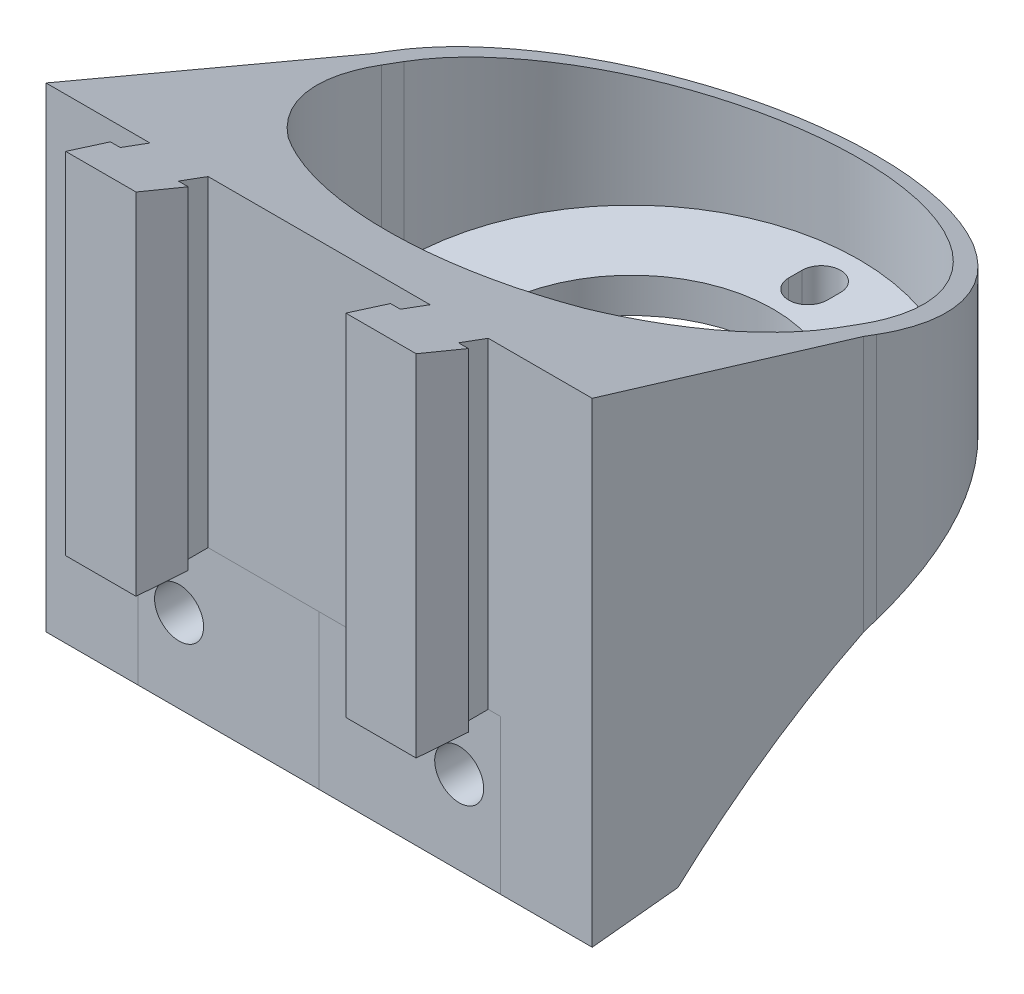
SolidWorks part; units mm, degrees
ref_plane "Front Plane" through (0, 0, 0) normal (0, 0, 1) x (1, 0, 0)
ref_plane "Top Plane" through (0, 0, 0) normal (0, 1, 0) x (1, 0, 0)
ref_plane "Right Plane" through (0, 0, 0) normal (1, 0, 0) x (0, 0, -1)
sketch "Sketch1" plane through (0, 0, 0) normal (0, 1, 0) x (1, 0, 0)
  line L208 (0, 28.6911) -> (0, 71.6911) construction
  line L209 (0, 59.2911) -> (-47.2537, 59.2911) construction
  line L210 (16.6412, 0.931) -> (17.2272, 1.5169) construction
  line L211 (14.3988, 4.3454) -> (13.8128, 3.7594) construction
  line L212 (13.8128, 10.4769) -> (14.3988, 9.891) construction
  line L213 (17.2272, 12.7194) -> (16.6412, 13.3054) construction
  line L214 (23.3588, 13.3054) -> (22.7728, 12.7194) construction
  line L215 (25.6012, 9.891) -> (26.1872, 10.4769) construction
  line L216 (26.1872, 3.7594) -> (25.6012, 4.3454) construction
  line L217 (22.7728, 1.5169) -> (23.3588, 0.931) construction
  line L218 (-29.6, -20.9818) -> (-29.6, -4.7818) construction
  line L219 (-38, -20.9818) -> (-29.6, -20.9818) construction
  line L220 (-38, -4.7818) -> (-38, -20.9818) construction
  line L221 (-29.6, -4.7818) -> (-38, -4.7818) construction
  line L222 (-23.3588, 0.931) -> (-22.7728, 1.5169) construction
  line L223 (-25.6012, 4.3454) -> (-26.1872, 3.7594) construction
  line L224 (-26.1872, 10.4769) -> (-25.6012, 9.891) construction
  line L225 (-22.7728, 12.7194) -> (-23.3588, 13.3054) construction
  line L226 (-16.6412, 13.3054) -> (-17.2272, 12.7194) construction
  line L227 (-14.3988, 9.891) -> (-13.8128, 10.4769) construction
  line L228 (-13.8128, 3.7594) -> (-14.3988, 4.3454) construction
  line L229 (-17.2272, 1.5169) -> (-16.6412, 0.931) construction
  line L230 (23.3588, -26.6946) -> (22.7728, -27.2806) construction
  line L231 (25.6012, -30.109) -> (26.1872, -29.5231) construction
  line L232 (26.1872, -36.2406) -> (25.6012, -35.6546) construction
  line L233 (22.7728, -38.4831) -> (23.3588, -39.069) construction
  line L234 (16.6412, -39.069) -> (17.2272, -38.4831) construction
  line L235 (14.3988, -35.6546) -> (13.8128, -36.2406) construction
  line L236 (13.8128, -29.5231) -> (14.3988, -30.109) construction
  line L237 (17.2272, -27.2806) -> (16.6412, -26.6946) construction
  line L238 (-31.2, -44.0818) -> (-38.4, -44.0818) construction
  line L239 (-31.2, -51.2818) -> (-31.2, -44.0818) construction
  line L240 (-38.4, -51.2818) -> (-31.2, -51.2818) construction
  line L241 (-38.4, -44.0818) -> (-38.4, -51.2818) construction
  line L242 (-16.6412, -26.6946) -> (-17.2272, -27.2806) construction
  line L243 (-14.3988, -30.109) -> (-13.8128, -29.5231) construction
  line L244 (-13.8128, -36.2406) -> (-14.3988, -35.6546) construction
  line L245 (-17.2272, -38.4831) -> (-16.6412, -39.069) construction
  line L246 (-23.3588, -39.069) -> (-22.7728, -38.4831) construction
  line L247 (-25.6012, -35.6546) -> (-26.1872, -36.2406) construction
  line L248 (-26.1872, -29.5231) -> (-25.6012, -30.109) construction
  line L249 (-22.7728, -27.2806) -> (-23.3588, -26.6946) construction
  line L250 (-38.4, 18.3182) -> (-31.2, 18.3182) construction
  line L251 (-38.4, 25.5182) -> (-38.4, 18.3182) construction
  line L252 (-31.2, 25.5182) -> (-38.4, 25.5182) construction
  line L253 (-31.2, 18.3182) -> (-31.2, 25.5182) construction
  line L254 (38.4, -44.0818) -> (31.2, -44.0818) construction
  line L255 (38.4, -51.2818) -> (38.4, -44.0818) construction
  line L256 (31.2, -51.2818) -> (38.4, -51.2818) construction
  line L257 (31.2, -44.0818) -> (31.2, -51.2818) construction
  line L258 (31.2, 18.2278) -> (38.4, 18.2278) construction
  line L259 (31.2, 25.5182) -> (31.2, 18.2278) construction
  line L260 (38.4, 25.5182) -> (31.2, 25.5182) construction
  line L261 (38.4, 18.2278) -> (38.4, 25.5182) construction
  line L262 (-8.1, 25.1182) -> (-8.1, 16.7182) construction
  line L263 (8.1, 25.1182) -> (-8.1, 25.1182) construction
  line L264 (8.1, 16.7182) -> (8.1, 25.1182) construction
  line L265 (-8.1, 16.7182) -> (8.1, 16.7182) construction
  line L266 (11.2, -37.6818) -> (11.2, -28.0818) construction
  line L267 (-9.2, -39.6818) -> (9.2, -39.6818) construction
  line L268 (-11.2, -28.0818) -> (-11.2, -37.6818) construction
  line L269 (-24.8, -24.0818) -> (-15.2, -24.0818) construction
  line L270 (-26.8, -3.6818) -> (-26.8, -22.0818) construction
  line L271 (-15.2, -1.6818) -> (-24.8, -1.6818) construction
  line L272 (-11.2, 11.9182) -> (-11.2, 2.3182) construction
  line L273 (9.2, 13.9182) -> (-9.2, 13.9182) construction
  line L274 (11.2, 2.3182) -> (11.2, 11.9182) construction
  line L275 (24.8, -1.6818) -> (15.2, -1.6818) construction
  line L276 (26.8, -22.0818) -> (26.8, -3.6818) construction
  line L277 (15.2, -24.0818) -> (24.8, -24.0818) construction
  line L278 (8.1, -42.4818) -> (-8.1, -42.4818) construction
  line L279 (8.1, -50.8818) -> (8.1, -42.4818) construction
  line L280 (-8.1, -50.8818) -> (8.1, -50.8818) construction
  line L281 (-8.1, -42.4818) -> (-8.1, -50.8818) construction
  line L282 (29.6, -4.7818) -> (29.6, -20.9818) construction
  line L283 (38, -4.7818) -> (29.6, -4.7818) construction
  line L284 (38, -20.9818) -> (38, -4.7818) construction
  line L285 (29.6, -20.9818) -> (38, -20.9818) construction
  line L286 (40, -51.8818) -> (40, -38.1318) construction
  line L287 (40, -38.1318) -> (39, -37.1318) construction
  line L288 (39, -37.1318) -> (36, -37.1318) construction
  line L289 (36, -37.1318) -> (36, -40.1318) construction
  line L290 (36, -40.1318) -> (37.6041, -40.1318) construction
  line L291 (38.0965, -40.7186) -> (37.9168, -41.7381) construction
  line L292 (37.0304, -42.4818) -> (32.3339, -42.4818) construction
  line L293 (30.2125, -41.6031) -> (29.6787, -41.0693) construction
  line L294 (28.8, -38.9479) -> (28.8, -26.8157) construction
  line L295 (29.6787, -24.6944) -> (30.2125, -24.1605) construction
  line L296 (32.3339, -23.2818) -> (37.0304, -23.2818) construction
  line L297 (37.9168, -24.0255) -> (38.0965, -25.045) construction
  line L298 (37.6041, -25.6318) -> (36, -25.6318) construction
  line L299 (36, -25.6318) -> (36, -28.6318) construction
  line L300 (36, -28.6318) -> (39, -28.6318) construction
  line L301 (39, -28.6318) -> (40, -27.6318) construction
  line L302 (40, -27.6318) -> (40, 1.8682) construction
  line L303 (40, 1.8682) -> (39, 2.8682) construction
  line L304 (39, 2.8682) -> (36, 2.8682) construction
  line L305 (36, 2.8682) -> (36, -0.1318) construction
  line L306 (36, -0.1318) -> (37.6041, -0.1318) construction
  line L307 (38.0965, -0.7186) -> (37.9168, -1.7381) construction
  line L308 (37.0304, -2.4818) -> (32.3339, -2.4818) construction
  line L309 (30.2125, -1.6031) -> (29.6787, -1.0693) construction
  line L310 (28.8, 1.0521) -> (28.8, 13.1843) construction
  line L311 (29.6787, 15.3056) -> (30.2125, 15.8395) construction
  line L312 (32.3339, 16.7182) -> (37.0304, 16.7182) construction
  line L313 (37.9168, 15.9745) -> (38.0965, 14.955) construction
  line L314 (37.6041, 14.3682) -> (36, 14.3682) construction
  line L315 (36, 14.3682) -> (36, 9.7607) construction
  line L316 (36, 9.7607) -> (39, 9.7607) construction
  line L317 (39, 9.7607) -> (40, 10.7607) construction
  line L318 (40, 10.7607) -> (40, 26.0836) construction
  line L319 (39, 27.0836) -> (25.25, 27.0836) construction
  line L320 (25.25, 27.0836) -> (24.25, 26.0836) construction
  line L321 (24.25, 26.0836) -> (24.25, 23.0836) construction
  line L322 (24.25, 23.0836) -> (27.25, 23.0836) construction
  line L323 (27.25, 23.0836) -> (27.25, 26.2607) construction
  line L324 (27.8368, 26.7531) -> (28.8563, 26.5733) construction
  line L325 (29.6, 25.687) -> (29.6, 19.4175) construction
  line L326 (28.7213, 17.2962) -> (28.1875, 16.7623) construction
  line L327 (26.0661, 15.8836) -> (13.9339, 15.8836) construction
  line L328 (11.8125, 16.7623) -> (11.2787, 17.2962) construction
  line L329 (10.4, 19.4175) -> (10.4, 24.1141) construction
  line L330 (11.1437, 25.0004) -> (12.1632, 25.1801) construction
  line L331 (12.75, 24.6877) -> (12.75, 23.0836) construction
  line L332 (12.75, 23.0836) -> (17.1652, 23.0836) construction
  line L333 (17.1652, 23.0836) -> (17.1652, 26.2414) construction
  line L334 (17.1652, 26.2414) -> (16.3229, 27.0836) construction
  line L335 (16.3229, 27.0836) -> (-14.75, 27.0836) construction
  line L336 (-14.75, 27.0836) -> (-15.75, 26.0836) construction
  line L337 (-15.75, 26.0836) -> (-15.75, 23.0836) construction
  line L338 (-15.75, 23.0836) -> (-12.75, 23.0836) construction
  line L339 (-12.75, 23.0836) -> (-12.75, 24.7223) construction
  line L340 (-12.1632, 25.2147) -> (-11.1437, 25.035) construction
  line L341 (-10.4, 24.1486) -> (-10.4, 19.4521) construction
  line L342 (-11.2787, 17.3307) -> (-11.8125, 16.7969) construction
  line L343 (-13.9339, 15.9182) -> (-26.0661, 15.9182) construction
  line L344 (-28.1875, 16.7969) -> (-28.7213, 17.3307) construction
  line L345 (-29.6, 19.4521) -> (-29.6, 24.1486) construction
  line L346 (-28.8563, 25.035) -> (-27.8368, 25.2147) construction
  line L347 (-27.25, 24.7223) -> (-27.25, 23.1182) construction
  line L348 (-27.25, 23.1182) -> (-24.25, 23.1182) construction
  line L349 (-24.25, 23.1182) -> (-24.25, 26.1182) construction
  line L350 (-24.25, 26.1182) -> (-25.25, 27.1182) construction
  line L351 (-25.25, 27.1182) -> (-39, 27.1182) construction
  line L352 (-40, 26.1182) -> (-40, 12.3682) construction
  line L353 (-40, 12.3682) -> (-39, 11.3682) construction
  line L354 (-39, 11.3682) -> (-36, 11.3682) construction
  line L355 (-36, 11.3682) -> (-36, 14.3682) construction
  line L356 (-36, 14.3682) -> (-37.6041, 14.3682) construction
  line L357 (-38.0965, 14.955) -> (-37.9168, 15.9745) construction
  line L358 (-37.0304, 16.7182) -> (-32.3339, 16.7182) construction
  line L359 (-30.2125, 15.8395) -> (-29.6787, 15.3056) construction
  line L360 (-28.8, 13.1843) -> (-28.8, 1.0521) construction
  line L361 (-29.6787, -1.0693) -> (-30.2125, -1.6031) construction
  line L362 (-32.3339, -2.4818) -> (-37.0304, -2.4818) construction
  line L363 (-37.9168, -1.7381) -> (-38.0965, -0.7186) construction
  line L364 (-37.6041, -0.1318) -> (-36, -0.1318) construction
  line L365 (-36, -0.1318) -> (-36, 2.8682) construction
  line L366 (-36, 2.8682) -> (-39, 2.8682) construction
  line L367 (-39, 2.8682) -> (-40, 1.8682) construction
  line L368 (-40, 1.8682) -> (-40, -27.6318) construction
  line L369 (-40, -27.6318) -> (-39, -28.6318) construction
  line L370 (-39, -28.6318) -> (-36, -28.6318) construction
  line L371 (-36, -28.6318) -> (-36, -25.6318) construction
  line L372 (-36, -25.6318) -> (-37.6041, -25.6318) construction
  line L373 (-38.0965, -25.045) -> (-37.9168, -24.0255) construction
  line L374 (-37.0304, -23.2818) -> (-32.3339, -23.2818) construction
  line L375 (-30.2125, -24.1605) -> (-29.6787, -24.6944) construction
  line L376 (-28.8, -26.8157) -> (-28.8, -38.9479) construction
  line L377 (-29.6787, -41.0693) -> (-30.2125, -41.6031) construction
  line L378 (-32.3339, -42.4818) -> (-37.0304, -42.4818) construction
  line L379 (-37.9168, -41.7381) -> (-38.0965, -40.7186) construction
  line L380 (-37.6041, -40.1318) -> (-36, -40.1318) construction
  line L381 (-36, -40.1318) -> (-36, -37.1318) construction
  line L382 (-36, -37.1318) -> (-39, -37.1318) construction
  line L383 (-39, -37.1318) -> (-40, -38.1318) construction
  line L384 (-40, -38.1318) -> (-40, -51.8818) construction
  line L385 (-39, -52.8818) -> (-25.25, -52.8818) construction
  line L386 (-25.25, -52.8818) -> (-24.25, -51.8818) construction
  line L387 (-24.25, -51.8818) -> (-24.25, -48.8818) construction
  line L388 (-24.25, -48.8818) -> (-27.25, -48.8818) construction
  line L389 (-27.25, -48.8818) -> (-27.25, -50.4859) construction
  line L390 (-27.8368, -50.9783) -> (-28.8563, -50.7986) construction
  line L391 (-29.6, -49.9123) -> (-29.6, -45.2157) construction
  line L392 (-28.7213, -43.0944) -> (-28.1875, -42.5605) construction
  line L393 (-26.0661, -41.6818) -> (-13.9339, -41.6818) construction
  line L394 (-11.8125, -42.5605) -> (-11.2787, -43.0944) construction
  line L395 (-10.4, -45.2157) -> (-10.4, -49.9123) construction
  line L396 (-11.1437, -50.7986) -> (-12.1632, -50.9783) construction
  line L397 (-12.75, -50.4859) -> (-12.75, -48.8818) construction
  line L398 (-12.75, -48.8818) -> (-15.75, -48.8818) construction
  line L399 (-15.75, -48.8818) -> (-15.75, -51.8818) construction
  line L400 (-15.75, -51.8818) -> (-14.75, -52.8818) construction
  line L401 (-14.75, -52.8818) -> (14.75, -52.8818) construction
  line L402 (14.75, -52.8818) -> (15.75, -51.8818) construction
  line L403 (15.75, -51.8818) -> (15.75, -48.8818) construction
  line L404 (15.75, -48.8818) -> (12.75, -48.8818) construction
  line L405 (12.75, -48.8818) -> (12.75, -50.4859) construction
  line L406 (12.1632, -50.9783) -> (11.1437, -50.7986) construction
  line L407 (10.4, -49.9123) -> (10.4, -45.2157) construction
  line L408 (11.2787, -43.0944) -> (11.8125, -42.5605) construction
  line L409 (13.9339, -41.6818) -> (26.0661, -41.6818) construction
  line L410 (28.1875, -42.5605) -> (28.7213, -43.0944) construction
  line L411 (29.6, -45.2157) -> (29.6, -49.9123) construction
  line L412 (28.8563, -50.7986) -> (27.8368, -50.9783) construction
  line L413 (27.25, -50.4859) -> (27.25, -48.8818) construction
  line L414 (27.25, -48.8818) -> (24.25, -48.8818) construction
  line L415 (24.25, -48.8818) -> (24.25, -51.8818) construction
  line L416 (24.25, -51.8818) -> (25.25, -52.8818) construction
  line L417 (25.25, -52.8818) -> (39, -52.8818) construction
  line L418 (0, 71.6911) -> (0, 68.4761) construction
  line L419 (34.9935, 71.6911) -> (34.9935, 68.4761)
  line L420 (-34.9935, 71.6911) -> (-34.9935, 68.4761)
  line L421 (0, 71.6911) -> (0, 70.0836) construction
  line L422 (32.9959, 71.6911) -> (32.9959, 70.0836) construction
  line L423 (-32.9959, 71.6911) -> (-32.9959, 70.0836) construction
  line L424 (-34.9935, 70.0836) -> (-34.8, 27.1182) construction
  line L427 (27.1, 71.6911) -> (27.0834, 67.963) construction
  line L430 (0, 71.6911) -> (0, 68.4761) construction
  line L431 (32.5, 71.6911) -> (32.5, 68.4761)
  line L432 (-32.5, 71.6911) -> (-32.5, 68.4761)
  line L433 (0, 71.6911) -> (0, 68.4761) construction
  line L436 (0, 98.7911) -> (0, 96.8911) construction
  line L437 (2.75, 98.7911) -> (2.75, 96.8911)
  line L438 (-2.75, 98.7911) -> (-2.75, 96.8911)
  line L439 (0, 70.0836) -> (54.1857, 70.0836) construction
  line L440 (0, 41.3761) -> (0, 43.2761) construction
  line L443 (0, 71.6911) -> (0, 68.4761) construction
  line L444 (20.25, 71.6911) -> (20.25, 68.4761)
  line L445 (-20.25, 71.6911) -> (-20.25, 68.4761)
  line L446 (2.75, 41.3761) -> (2.75, 43.2761)
  line L447 (-2.75, 41.3761) -> (-2.75, 43.2761)
  line L448 (25.6055, 71.0336) -> (25.597, 69.1336) construction
  line L449 (28.3555, 71.0214) -> (28.347, 69.1214)
  line L450 (22.8555, 71.0459) -> (22.847, 69.1459)
  line L451 (-25.6055, 71.0336) -> (-25.597, 69.1336) construction
  line L452 (-28.3555, 71.0214) -> (-28.347, 69.1214)
  line L453 (-22.8555, 71.0459) -> (-22.847, 69.1459)
  circle A112 centre (0, 71.6911) radius 12.4 construction
  arc A113 (0, 38.6911) -> (-30.5817, 59.2911) centre (0, 71.6911) ccw construction
  circle A114 centre (0, 71.6911) radius 20.25 construction
  arc A115 (34.9935, 71.0158) -> (-34.9935, 71.0158) centre (0, 71.6911) ccw construction
  circle A116 centre (0, 71.6911) radius 27.1 construction
  circle A117 centre (0, 98.7911) radius 1.9 construction
  circle A118 centre (-27.1, 71.6911) radius 1.9 construction
  circle A119 centre (0, 44.5911) radius 1.9 construction
  circle A120 centre (27.1, 71.6911) radius 1.9 construction
  arc A121 (17.2272, 1.5169) -> (22.7728, 1.5169) centre (20, 7.1182) ccw construction
  arc A122 (13.8128, 3.7594) -> (16.6412, 0.931) centre (15.227, 2.3452) ccw construction
  arc A123 (14.3988, 9.891) -> (14.3988, 4.3454) centre (20, 7.1182) ccw construction
  arc A124 (16.6412, 13.3054) -> (13.8128, 10.4769) centre (15.227, 11.8912) ccw construction
  arc A125 (22.7728, 12.7194) -> (17.2272, 12.7194) centre (20, 7.1182) ccw construction
  arc A126 (26.1872, 10.4769) -> (23.3588, 13.3054) centre (24.773, 11.8912) ccw construction
  arc A127 (25.6012, 4.3454) -> (25.6012, 9.891) centre (20, 7.1182) ccw construction
  arc A128 (23.3588, 0.931) -> (26.1872, 3.7594) centre (24.773, 2.3452) ccw construction
  arc A129 (-22.7728, 1.5169) -> (-17.2272, 1.5169) centre (-20, 7.1182) ccw construction
  arc A130 (-26.1872, 3.7594) -> (-23.3588, 0.931) centre (-24.773, 2.3452) ccw construction
  arc A131 (-25.6012, 9.891) -> (-25.6012, 4.3454) centre (-20, 7.1182) ccw construction
  arc A132 (-23.3588, 13.3054) -> (-26.1872, 10.4769) centre (-24.773, 11.8912) ccw construction
  arc A133 (-17.2272, 12.7194) -> (-22.7728, 12.7194) centre (-20, 7.1182) ccw construction
  arc A134 (-13.8128, 10.4769) -> (-16.6412, 13.3054) centre (-15.227, 11.8912) ccw construction
  arc A135 (-14.3988, 4.3454) -> (-14.3988, 9.891) centre (-20, 7.1182) ccw construction
  arc A136 (-16.6412, 0.931) -> (-13.8128, 3.7594) centre (-15.227, 2.3452) ccw construction
  arc A137 (22.7728, -27.2806) -> (17.2272, -27.2806) centre (20, -32.8818) ccw construction
  arc A138 (26.1872, -29.5231) -> (23.3588, -26.6946) centre (24.773, -28.1088) ccw construction
  arc A139 (25.6012, -35.6546) -> (25.6012, -30.109) centre (20, -32.8818) ccw construction
  arc A140 (23.3588, -39.069) -> (26.1872, -36.2406) centre (24.773, -37.6548) ccw construction
  arc A141 (17.2272, -38.4831) -> (22.7728, -38.4831) centre (20, -32.8818) ccw construction
  arc A142 (13.8128, -36.2406) -> (16.6412, -39.069) centre (15.227, -37.6548) ccw construction
  arc A143 (14.3988, -30.109) -> (14.3988, -35.6546) centre (20, -32.8818) ccw construction
  arc A144 (16.6412, -26.6946) -> (13.8128, -29.5231) centre (15.227, -28.1088) ccw construction
  arc A145 (-17.2272, -27.2806) -> (-22.7728, -27.2806) centre (-20, -32.8818) ccw construction
  arc A146 (-13.8128, -29.5231) -> (-16.6412, -26.6946) centre (-15.227, -28.1088) ccw construction
  arc A147 (-14.3988, -35.6546) -> (-14.3988, -30.109) centre (-20, -32.8818) ccw construction
  arc A148 (-16.6412, -39.069) -> (-13.8128, -36.2406) centre (-15.227, -37.6548) ccw construction
  arc A149 (-22.7728, -38.4831) -> (-17.2272, -38.4831) centre (-20, -32.8818) ccw construction
  arc A150 (-26.1872, -36.2406) -> (-23.3588, -39.069) centre (-24.773, -37.6548) ccw construction
  arc A151 (-25.6012, -30.109) -> (-25.6012, -35.6546) centre (-20, -32.8818) ccw construction
  arc A152 (-23.3588, -26.6946) -> (-26.1872, -29.5231) centre (-24.773, -28.1088) ccw construction
  arc A153 (15.2, -24.0818) -> (11.2, -28.0818) centre (15.2, -28.0818) ccw construction
  arc A154 (9.2, -39.6818) -> (11.2, -37.6818) centre (9.2, -37.6818) ccw construction
  arc A155 (-11.2, -37.6818) -> (-9.2, -39.6818) centre (-9.2, -37.6818) ccw construction
  arc A156 (-11.2, -28.0818) -> (-15.2, -24.0818) centre (-15.2, -28.0818) ccw construction
  arc A157 (-26.8, -22.0818) -> (-24.8, -24.0818) centre (-24.8, -22.0818) ccw construction
  arc A158 (-24.8, -1.6818) -> (-26.8, -3.6818) centre (-24.8, -3.6818) ccw construction
  arc A159 (-15.2, -1.6818) -> (-11.2, 2.3182) centre (-15.2, 2.3182) ccw construction
  arc A160 (-9.2, 13.9182) -> (-11.2, 11.9182) centre (-9.2, 11.9182) ccw construction
  arc A161 (11.2, 11.9182) -> (9.2, 13.9182) centre (9.2, 11.9182) ccw construction
  arc A162 (11.2, 2.3182) -> (15.2, -1.6818) centre (15.2, 2.3182) ccw construction
  arc A163 (26.8, -3.6818) -> (24.8, -1.6818) centre (24.8, -3.6818) ccw construction
  arc A164 (24.8, -24.0818) -> (26.8, -22.0818) centre (24.8, -22.0818) ccw construction
  arc A165 (39, -52.8818) -> (40, -51.8818) centre (39, -51.8818) ccw construction
  arc A166 (38.0965, -40.7186) -> (37.6041, -40.1318) centre (37.6041, -40.6318) ccw construction
  arc A167 (37.0304, -42.4818) -> (37.9168, -41.7381) centre (37.0304, -41.5818) ccw construction
  arc A168 (30.2125, -41.6031) -> (32.3339, -42.4818) centre (32.3339, -39.4818) ccw construction
  arc A169 (28.8, -38.9479) -> (29.6787, -41.0693) centre (31.8, -38.9479) ccw construction
  arc A170 (29.6787, -24.6944) -> (28.8, -26.8157) centre (31.8, -26.8157) ccw construction
  arc A171 (32.3339, -23.2818) -> (30.2125, -24.1605) centre (32.3339, -26.2818) ccw construction
  arc A172 (37.9168, -24.0255) -> (37.0304, -23.2818) centre (37.0304, -24.1818) ccw construction
  arc A173 (37.6041, -25.6318) -> (38.0965, -25.045) centre (37.6041, -25.1318) ccw construction
  arc A174 (38.0965, -0.7186) -> (37.6041, -0.1318) centre (37.6041, -0.6318) ccw construction
  arc A175 (37.0304, -2.4818) -> (37.9168, -1.7381) centre (37.0304, -1.5818) ccw construction
  arc A176 (30.2125, -1.6031) -> (32.3339, -2.4818) centre (32.3339, 0.5182) ccw construction
  arc A177 (28.8, 1.0521) -> (29.6787, -1.0693) centre (31.8, 1.0521) ccw construction
  arc A178 (29.6787, 15.3056) -> (28.8, 13.1843) centre (31.8, 13.1843) ccw construction
  arc A179 (32.3339, 16.7182) -> (30.2125, 15.8395) centre (32.3339, 13.7182) ccw construction
  arc A180 (37.9168, 15.9745) -> (37.0304, 16.7182) centre (37.0304, 15.8182) ccw construction
  arc A181 (37.6041, 14.3682) -> (38.0965, 14.955) centre (37.6041, 14.8682) ccw construction
  arc A182 (40, 26.0836) -> (39, 27.0836) centre (39, 26.0836) ccw construction
  arc A183 (27.8368, 26.7531) -> (27.25, 26.2607) centre (27.75, 26.2607) ccw construction
  arc A184 (29.6, 25.687) -> (28.8563, 26.5733) centre (28.7, 25.687) ccw construction
  arc A185 (28.7213, 17.2962) -> (29.6, 19.4175) centre (26.6, 19.4175) ccw construction
  arc A186 (26.0661, 15.8836) -> (28.1875, 16.7623) centre (26.0661, 18.8836) ccw construction
  arc A187 (11.8125, 16.7623) -> (13.9339, 15.8836) centre (13.9339, 18.8836) ccw construction
  arc A188 (10.4, 19.4175) -> (11.2787, 17.2962) centre (13.4, 19.4175) ccw construction
  arc A189 (11.1437, 25.0004) -> (10.4, 24.1141) centre (11.3, 24.1141) ccw construction
  arc A190 (12.75, 24.6877) -> (12.1632, 25.1801) centre (12.25, 24.6877) ccw construction
  arc A191 (-12.1632, 25.2147) -> (-12.75, 24.7223) centre (-12.25, 24.7223) ccw construction
  arc A192 (-10.4, 24.1486) -> (-11.1437, 25.035) centre (-11.3, 24.1486) ccw construction
  arc A193 (-11.2787, 17.3307) -> (-10.4, 19.4521) centre (-13.4, 19.4521) ccw construction
  arc A194 (-13.9339, 15.9182) -> (-11.8125, 16.7969) centre (-13.9339, 18.9182) ccw construction
  arc A195 (-28.1875, 16.7969) -> (-26.0661, 15.9182) centre (-26.0661, 18.9182) ccw construction
  arc A196 (-29.6, 19.4521) -> (-28.7213, 17.3307) centre (-26.6, 19.4521) ccw construction
  arc A197 (-28.8563, 25.035) -> (-29.6, 24.1486) centre (-28.7, 24.1486) ccw construction
  arc A198 (-27.25, 24.7223) -> (-27.8368, 25.2147) centre (-27.75, 24.7223) ccw construction
  arc A199 (-39, 27.1182) -> (-40, 26.1182) centre (-39, 26.1182) ccw construction
  arc A200 (-38.0965, 14.955) -> (-37.6041, 14.3682) centre (-37.6041, 14.8682) ccw construction
  arc A201 (-37.0304, 16.7182) -> (-37.9168, 15.9745) centre (-37.0304, 15.8182) ccw construction
  arc A202 (-30.2125, 15.8395) -> (-32.3339, 16.7182) centre (-32.3339, 13.7182) ccw construction
  arc A203 (-28.8, 13.1843) -> (-29.6787, 15.3056) centre (-31.8, 13.1843) ccw construction
  arc A204 (-29.6787, -1.0693) -> (-28.8, 1.0521) centre (-31.8, 1.0521) ccw construction
  arc A205 (-32.3339, -2.4818) -> (-30.2125, -1.6031) centre (-32.3339, 0.5182) ccw construction
  arc A206 (-37.9168, -1.7381) -> (-37.0304, -2.4818) centre (-37.0304, -1.5818) ccw construction
  arc A207 (-37.6041, -0.1318) -> (-38.0965, -0.7186) centre (-37.6041, -0.6318) ccw construction
  arc A208 (-38.0965, -25.045) -> (-37.6041, -25.6318) centre (-37.6041, -25.1318) ccw construction
  arc A209 (-37.0304, -23.2818) -> (-37.9168, -24.0255) centre (-37.0304, -24.1818) ccw construction
  arc A210 (-30.2125, -24.1605) -> (-32.3339, -23.2818) centre (-32.3339, -26.2818) ccw construction
  arc A211 (-28.8, -26.8157) -> (-29.6787, -24.6944) centre (-31.8, -26.8157) ccw construction
  arc A212 (-29.6787, -41.0693) -> (-28.8, -38.9479) centre (-31.8, -38.9479) ccw construction
  arc A213 (-32.3339, -42.4818) -> (-30.2125, -41.6031) centre (-32.3339, -39.4818) ccw construction
  arc A214 (-37.9168, -41.7381) -> (-37.0304, -42.4818) centre (-37.0304, -41.5818) ccw construction
  arc A215 (-37.6041, -40.1318) -> (-38.0965, -40.7186) centre (-37.6041, -40.6318) ccw construction
  arc A216 (-40, -51.8818) -> (-39, -52.8818) centre (-39, -51.8818) ccw construction
  arc A217 (-27.8368, -50.9783) -> (-27.25, -50.4859) centre (-27.75, -50.4859) ccw construction
  arc A218 (-29.6, -49.9123) -> (-28.8563, -50.7986) centre (-28.7, -49.9123) ccw construction
  arc A219 (-28.7213, -43.0944) -> (-29.6, -45.2157) centre (-26.6, -45.2157) ccw construction
  arc A220 (-26.0661, -41.6818) -> (-28.1875, -42.5605) centre (-26.0661, -44.6818) ccw construction
  arc A221 (-11.8125, -42.5605) -> (-13.9339, -41.6818) centre (-13.9339, -44.6818) ccw construction
  arc A222 (-10.4, -45.2157) -> (-11.2787, -43.0944) centre (-13.4, -45.2157) ccw construction
  arc A223 (-11.1437, -50.7986) -> (-10.4, -49.9123) centre (-11.3, -49.9123) ccw construction
  arc A224 (-12.75, -50.4859) -> (-12.1632, -50.9783) centre (-12.25, -50.4859) ccw construction
  arc A225 (12.1632, -50.9783) -> (12.75, -50.4859) centre (12.25, -50.4859) ccw construction
  arc A226 (10.4, -49.9123) -> (11.1437, -50.7986) centre (11.3, -49.9123) ccw construction
  arc A227 (11.2787, -43.0944) -> (10.4, -45.2157) centre (13.4, -45.2157) ccw construction
  arc A228 (13.9339, -41.6818) -> (11.8125, -42.5605) centre (13.9339, -44.6818) ccw construction
  arc A229 (28.1875, -42.5605) -> (26.0661, -41.6818) centre (26.0661, -44.6818) ccw construction
  arc A230 (29.6, -45.2157) -> (28.7213, -43.0944) centre (26.6, -45.2157) ccw construction
  arc A231 (28.8563, -50.7986) -> (29.6, -49.9123) centre (28.7, -49.9123) ccw construction
  arc A232 (27.25, -50.4859) -> (27.8368, -50.9783) centre (27.75, -50.4859) ccw construction
  arc A233 (34.9935, 71.6911) -> (-34.9935, 71.6911) centre (0, 71.6911) ccw
  arc A234 (-34.9935, 68.4761) -> (34.9935, 68.4761) centre (0, 68.4761) ccw
  arc A235 (32.9959, 71.6911) -> (-32.9959, 71.6911) centre (0, 71.6911) ccw construction
  arc A236 (-32.9959, 70.0836) -> (32.9959, 70.0836) centre (0, 70.0836) ccw construction
  arc A241 (32.5, 71.6911) -> (-32.5, 71.6911) centre (0, 71.6911) ccw
  arc A242 (-32.5, 68.4761) -> (32.5, 68.4761) centre (0, 68.4761) ccw
  arc A244 (-27.0807, 67.8362) -> (27.0834, 67.963) centre (0, 68.4761) ccw construction
  arc A245 (27.0207, 73.6541) -> (-27.0207, 73.6541) centre (0, 71.6911) ccw construction
  arc A246 (2.75, 98.7911) -> (-2.75, 98.7911) centre (0, 98.7911) ccw
  arc A247 (-2.75, 96.8911) -> (2.75, 96.8911) centre (0, 96.8911) ccw
  arc A250 (20.25, 71.6911) -> (-20.25, 71.6911) centre (0, 71.6911) ccw
  arc A251 (-20.25, 68.4761) -> (20.25, 68.4761) centre (0, 68.4761) ccw
  arc A252 (2.75, 41.3761) -> (-2.75, 41.3761) centre (0, 41.3761) cw
  arc A253 (-2.75, 43.2761) -> (2.75, 43.2761) centre (0, 43.2761) cw
  arc A254 (28.3555, 71.0214) -> (22.8555, 71.0459) centre (25.6055, 71.0336) ccw
  arc A255 (22.847, 69.1459) -> (28.347, 69.1214) centre (25.597, 69.1336) ccw
  arc A256 (-28.3555, 71.0214) -> (-22.8555, 71.0459) centre (-25.6055, 71.0336) cw
  arc A257 (-22.847, 69.1459) -> (-28.347, 69.1214) centre (-25.597, 69.1336) cw
  point P0 (0, 70.0836)
  point P6 (0, 70.8874)
  point P21 (25.6012, 70.0836)
  point P23 (0, 70.0836)
  point P36 (0, 70.0836)
  point P39 (0, 97.8411)
  point P53 (0, 42.3261)
  point P56 (0, 70.0836)
  point P61 (20.25, 70.0836)
  point P68 (-25.6012, 70.0836)
  point P453 (0, 71.6911)
  dimension "D3" = 40.5
  dimension "D4" = 43
  dimension "D5" = 70
  dimension "D6" = 5.9
  dimension "D7" = 3.8
  dimension "D11" = 40.5
  dimension "D2" = 80
  dimension "D9" = 65
  dimension "D10" = 1.9
  dimension "D12" = 1.9
  dimension "D8" = 4
extrude "Boss-Extrude1" add sketch "Sketch1" along normal blind 5 contours L432 A242 L431 A241 A255 L450 A254 L449 A251 L445 A250 L444 A247 L438 A246 L437 L447 A253 L446 A252 L453 A257 L452 A256 region at (31.5578, 0, -70.0836)
extrude "Boss-Extrude3" add sketch "Sketch1<4>" along normal blind 50 and the other way blind 22 contours L432 A242 L431 A241 | L420 A234 L419 A233
sketch "Sketch1<4>" plane through (0, 0, 0) normal (0, 1, 0) x (1, 0, 0) same geometry as "Sketch1"
sketch "Sketch2" plane through (0, 0, 0) normal (0, 1, 0) x (1, 0, 0)
  line L0 (39, 27.0836) -> (25.25, 27.0836) construction
  line L1 (-15.85, 22.8385) -> (-14.4427, 22.8385)
  line L2 (-14.4427, 22.8385) -> (-14.9776, 15.9182)
  line L3 (-25.5573, 22.8385) -> (-25.0224, 15.9182)
  line L6 (-24.15, 22.8385) -> (-25.5573, 22.8385)
  line L7 (24.15, 22.8385) -> (25.5573, 22.8385)
  line L8 (25.5573, 22.8385) -> (25.0224, 15.9182)
  line L9 (15.85, 22.8385) -> (14.4427, 22.8385)
  line L10 (-25.25, 27.0836) -> (-24.15, 27.0836)
  line L11 (-24.15, 27.0836) -> (-24.15, 22.8385)
  line L12 (14.4427, 22.8385) -> (14.9776, 15.9182)
  line L16 (39, 27.0836) -> (25.25, 27.0836)
  line L32 (39, 27.0836) -> (34.9647, 70.1198)
  line L34 (0, 28.6911) -> (0, 25.1182) construction
  line L35 (8.1, 25.1182) -> (-8.1, 25.1182) construction
  line L38 (-39, 27.0836) -> (-34.9647, 70.1198)
  line L53 (-39, 27.0836) -> (-25.25, 27.0836)
  line L58 (-13.9339, 15.9182) -> (-26.0661, 15.9182) construction
  line L59 (-25.0224, 15.9182) -> (-14.9776, 15.9182)
  line L60 (-20, 15.9182) -> (-20, 17.6656) construction
  line L61 (-14.75, 27.0836) -> (-15.85, 27.0836)
  line L62 (-15.85, 27.0836) -> (-15.85, 22.8385)
  line L63 (-24.25, 23.1182) -> (-24.25, 26.1182) construction
  line L64 (25.25, 27.0836) -> (24.15, 27.0836)
  line L65 (24.15, 27.0836) -> (24.15, 22.8385)
  line L66 (25.0224, 15.9182) -> (14.9776, 15.9182)
  line L67 (15.85, 27.0836) -> (15.85, 22.8385)
  line L68 (14.75, 27.0836) -> (15.85, 27.0836)
  line L69 (-14.75, 27.0836) -> (14.75, 27.0836)
  circle A14 centre (0, 71.6911) radius 35 construction
  arc A27 (-34.9647, 70.1198) -> (34.9647, 70.1198) centre (0, 71.6911) ccw
  dimension "D1" = 0.1
extrude "Boss-Extrude4" add sketch "Sketch2" along normal blind 50 and the other way blind 22
ref_plane "Plane2" through (0, 0, -70) normal (0, 0, 1) x (1, 0, 0)
sketch "Sketch7" plane through (0, 0, -70) normal (0, 0, 1) x (1, 0, 0)
  line L0 (0, 0) -> (0, 50) construction
  line L1 (-15.85, 50) -> (15.85, 50) construction
  circle A5 centre (-20, -10.1255) radius 8
  circle A8 centre (20, -10.1255) radius 8
  dimension "D1" = 16
  dimension "D2" = 16
sketch "Sketch6" plane through (0, 0, -70) normal (0, 0, 1) x (1, 0, 0)
  line L0 (-20, 50) -> (-20, -19.8018) construction
  line L1 (-25.0224, 50) -> (-14.9776, 50) construction
  line L2 (0, 50) -> (0, -18.6146) construction
  line L3 (-15.85, 50) -> (15.85, 50) construction
  circle A0 centre (-20, -10.1306) radius 3.5
  circle A1 centre (20, -10.1306) radius 3.5
ref_plane "Plane1" through (0, 0, 0) normal (0, 1, 0) x (1, 0, 0)
sketch "Sketch4" plane through (0, 0, 0) normal (0, 1, 0) x (1, 0, 0)
  line L0 (-25.25, 27.1182) -> (25.8812, 27.0836)
  line L1 (39, 27.0836) -> (25.25, 27.0836) construction
  line L2 (25.8812, 27.0836) -> (32.125, 22.8911)
  line L3 (32.125, 22.8911) -> (32.3339, 13.7182)
  line L4 (32.3339, 13.7182) -> (0, 13.9182)
  line L5 (9.2, 13.9182) -> (-9.2, 13.9182) construction
  line L6 (0, 13.7182) -> (0, 6.1314) construction
  line L7 (-32.3339, 13.7182) -> (0, 13.9182)
  line L8 (-32.125, 22.8911) -> (-32.3339, 13.7182)
  line L9 (-25.8812, 27.0836) -> (-32.125, 22.8911)
  line L10 (25.25, 27.1182) -> (-25.8812, 27.0836)
sketch "Sketch8" plane through (0, 0, 0) normal (1, 0, 0) x (0, 0, -1)
  line L1 (15.9182, 50) -> (106.6846, 50)
  line L2 (106.6846, 50) -> (71.6911, 50) construction
  line L5 (106.6846, 50) -> (106.6846, 16.6107)
  line L6 (106.6846, 16.6107) -> (15.9182, 50)
  line L9 (106.6846, 0) -> (71.6911, 0) construction
  line L10 (106.6911, 0) -> (71.0158, 0) construction
  line L11 (69.8129, -22) -> (27.0836, -22) construction
  line L12 (106.6846, 0) -> (106.6846, -22)
  line L13 (106.6846, -22) -> (40.5882, -22)
  spline S0 degree 2 poles (106.6846, 0) (69.6008, -0.6107) (40.5882, -22) knots 0 0 0 1 1 1
extrude "Cut-Extrude3" cut sketch "Sketch8" against normal mid plane 100
extrude "Cut-Extrude7" cut sketch "Sketch6" along normal blind 74
extrude "Cut-Extrude8" cut sketch "Sketch7" along normal blind 35
extrude "Cut-Extrude9" cut sketch "Sketch4" against normal blind 35 contours L0 L10 L9 L8 L7 L4 L3 L2 region at (0, 0, -20.2808)
sketch "Sketch9" plane through (0, 0, 0) normal (0, -1, 0) x (1, 0, 0)
  line L4 (-20.25, -68.4761) -> (-20.25, -71.6911)
  line L5 (20.25, -71.6911) -> (20.25, -68.4761)
  line L6 (-22.25, -68.4761) -> (-22.25, -71.6911)
  line L7 (22.25, -71.6911) -> (22.25, -68.4761)
  line L8 (-22.25, -68.4761) -> (-22.25, -71.6911)
  line L9 (22.25, -71.6911) -> (22.25, -68.4761)
  arc A15 (-20.25, -71.6911) -> (20.25, -71.6911) centre (0, -71.6911) ccw
  arc A16 (20.25, -68.4761) -> (-20.25, -68.4761) centre (0, -68.4761) ccw
  arc A17 (-22.25, -71.6911) -> (22.25, -71.6911) centre (0, -71.6911) ccw
  arc A18 (22.25, -68.4761) -> (-22.25, -68.4761) centre (0, -68.4761) ccw
  arc A19 (-22.25, -71.6911) -> (22.25, -71.6911) centre (0, -71.6911) ccw
  arc A20 (22.25, -68.4761) -> (-22.25, -68.4761) centre (0, -68.4761) ccw
  dimension "D1" = 2
  dimension "D2" = 2
